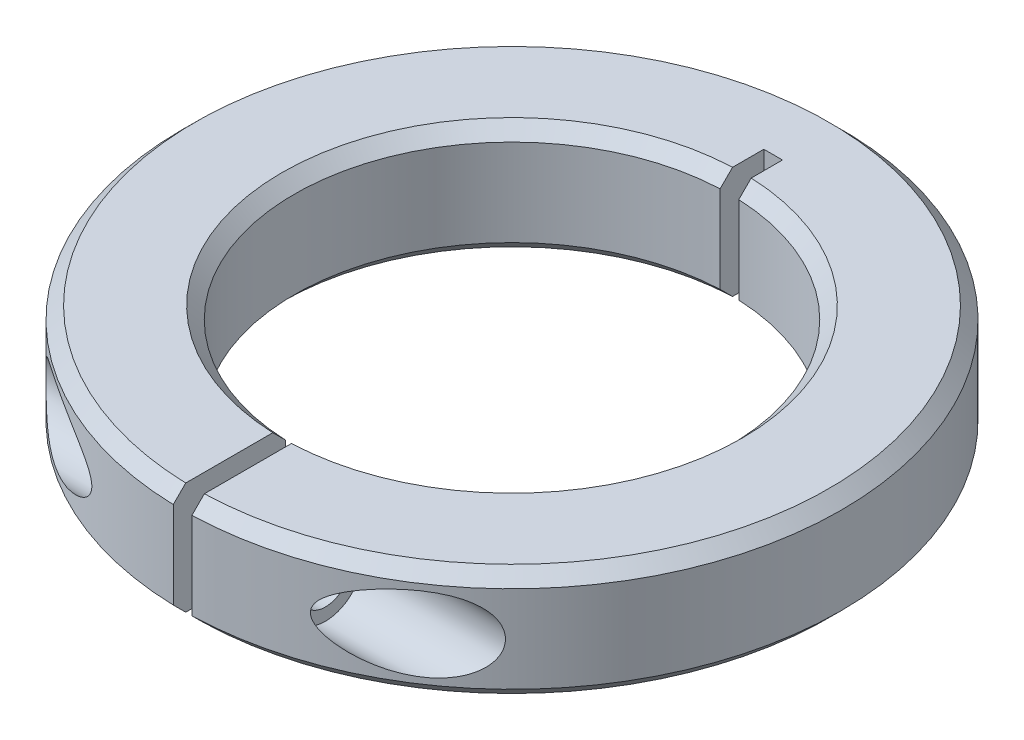
SolidWorks part; units mm, degrees
ref_plane "Front Plane" through (0, 0, 0) normal (0, 0, 1) x (1, 0, 0)
ref_plane "Top Plane" through (0, 0, 0) normal (0, 1, 0) x (1, 0, 0)
ref_plane "Right Plane" through (0, 0, 0) normal (1, 0, 0) x (0, 0, -1)
sketch "Sketch1" plane through (0, 0, 0) normal (0, 1, 0) x (1, 0, 0)
  line L0 (-0.75, 21) -> (0.75, 21)
  line L2 (-0.75, -26.4894) -> (-0.75, -17.4839)
  line L4 (0.75, -26.4894) -> (0.75, -17.4839)
  line L7 (0, 21) -> (0, 22.406) construction
  line L8 (-0.75, 17.4839) -> (-0.75, 21)
  line L9 (0.75, 17.4839) -> (0.75, 21)
  arc A0 (-0.75, 17.4839) -> (-0.75, -17.4839) centre (0, 0) ccw
  arc A1 (0.75, -26.4894) -> (-0.75, -26.4894) centre (0, 0) ccw
  arc A2 (0.75, -17.4839) -> (0.75, 17.4839) centre (0, 0) ccw
  point P4 (0, 17.5)
  dimension "D1" = 35
  dimension "D2" = 9
  dimension "D3" = 1.5
  dimension "D4" = 21
extrude "Boss-Extrude1" add sketch "Sketch1" along normal blind 9
chamfer "Chamfer1" distance 1 angle 45 6 edges at (-17.5, 0, 0) (17.5, 0, 0) (0, 0, -26.5) (0, 9, -26.5) (17.5, 9, 0) (-17.5, 9, 0)
sketch "Sketch2" plane through (0, 0, 0) normal (1, 0, 0) x (0, 0, -1)
  line L0 (-26.4894, 4.5) -> (-1.6098, 4.5) construction
  line L1 (-26.4894, 8) -> (-26.4894, 1) construction
  circle A0 centre (-22, 4.5) radius 3
  circle A1 centre (-22, 4.5) radius 2
  dimension "D1" = 6
  dimension "D2" = 4
  dimension "D3" = 22
extrude "Cut-Extrude2" cut sketch "Sketch2" against normal through all both and the other way through all contours A1 L0 | L0 A1 | L0 A0 A1 | A0 L0 A1 region at (0, 6.5671, 22) region at (0, 3.6512, 22) region at (0, 5.3488, 22) region at (0, 4.4329, 19.5)
extrude "Boss-Extrude2" add sketch "Sketch2<3>" along normal mid plane 14
sketch "Sketch2<3>" plane through (0, 0, 0) normal (1, 0, 0) x (0, 0, -1) same geometry as "Sketch2"
sketch "Sketch3" plane through (0, 9, 0) normal (0, 1, 0) x (1, 0, 0)
  line L1 (-0.75, -18.4848) -> (0.75, -18.4848)
  line L2 (-0.75, -18.4848) -> (-0.75, -25.489)
  line L3 (-0.75, -25.489) -> (0.75, -25.489)
  line L4 (0.75, -18.4848) -> (0.75, -25.489)
extrude "Cut-Extrude3" cut sketch "Sketch3" against normal through all both and the other way through all
